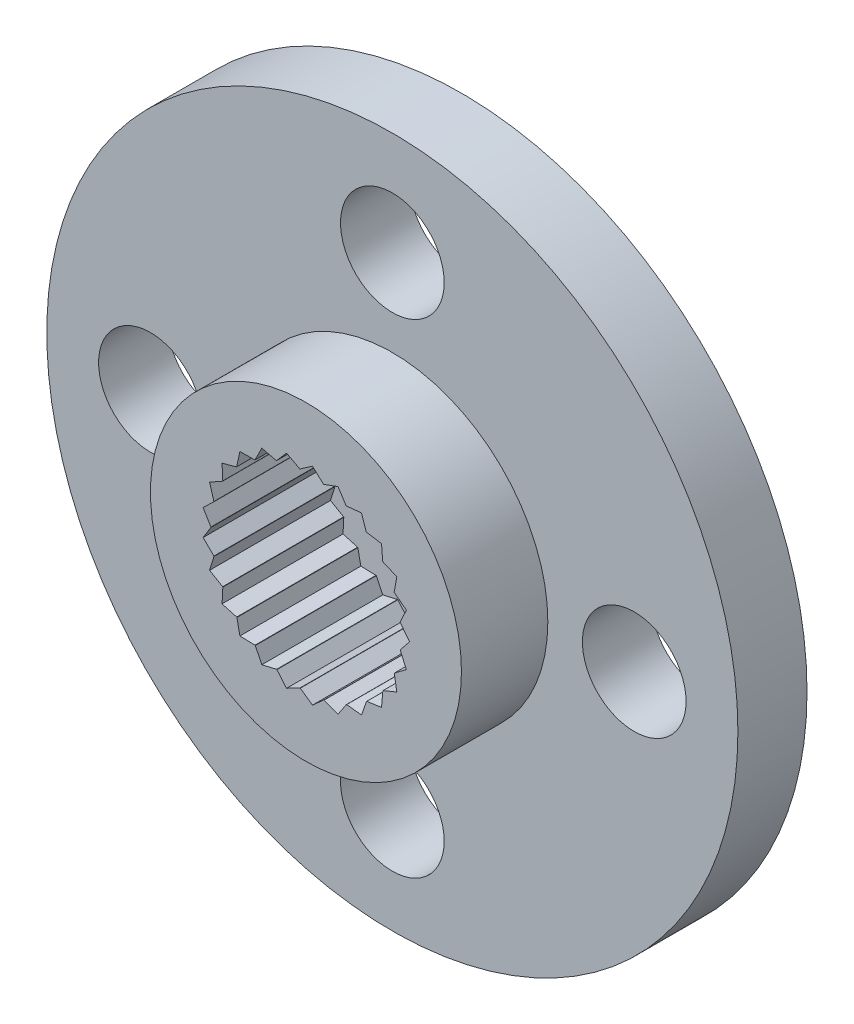
SolidWorks part; units mm, degrees
ref_plane "Front Plane" through (0, 0, 0) normal (0, 0, 1) x (1, 0, 0)
ref_plane "Top Plane" through (0, 0, 0) normal (0, 1, 0) x (1, 0, 0)
ref_plane "Right Plane" through (0, 0, 0) normal (1, 0, 0) x (0, 0, -1)
sketch "Sketch1" plane through (0, 0, 0) normal (0, 0, 1) x (1, 0, 0)
  circle A0 centre (0, 0) radius 10
  circle A1 centre (0, 0) radius 7 construction
  circle A2 centre (0, 7) radius 1.5
  circle A3 centre (7, 0) radius 1.5
  circle A4 centre (0, -7) radius 1.5
  circle A5 centre (-7, 0) radius 1.5
  circle A6 centre (0, 0) radius 4.5
  dimension "D1" = 20
  dimension "D2" = 3
  dimension "D3" = 4
extrude "Boss-Extrude1" add sketch "Sketch1" along normal blind 2
extrude "Boss-Extrude2" add sketch "Sketch1<2>" along normal blind 4.5 contours A6 region at (0, 0, 0)
sketch "Sketch1<2>" plane through (0, 0, 0) normal (0, 0, 1) x (1, 0, 0) same geometry as "Sketch1"
sketch "Sketch2" plane through (0, 0, 0) normal (0, 0, -1) x (-1, 0, 0)
  circle A0 centre (0, 0) radius 1.5
extrude "Cut-Extrude1" cut sketch "Sketch2" against normal blind 4.5
sketch "Sketch3" plane through (0, 0, 4.5) normal (0, 0, 1) x (1, 0, 0)
  circle A0 centre (0, 0) radius 2.75
extrude "Cut-Extrude2" cut sketch "Sketch3" against normal blind 3.5
sketch "Sketch4" plane through (0, 0, 4.5) normal (0, 0, 1) x (1, 0, 0)
  line L0 (0, 0) -> (-3, 0)
  line L1 (0, 0) -> (-2.9763, 0.376)
  line L2 (0, 0) -> (-2.9083, 0.7359)
  line L3 (-2.75, 0) -> (-2.9763, 0.376)
  line L4 (-2.666, 0.6746) -> (-2.9763, 0.376)
  circle A0 centre (0, 0) radius 3
  circle A1 centre (0, 0) radius 2.75 construction
  circle A2 centre (0, 0) radius 2.75 construction
  circle A3 centre (0, 0) radius 2.75
  circle M6 centre (0, 0) radius 2.75
  dimension "D1" = 7.2
  dimension "D2" = 14.2
extrude "Cut-Extrude3" cut sketch "Sketch4" against normal blind 3.5 contours L4 L1 M6 | L3 L1 M6 region at (-2.8205, 0.2422, 4.5) region at (-2.7928, 0.4638, 4.5)
pattern_circular "CirPattern1" count 25 over 360 about axis through (0, 0, 4.5) along (0, 0, -1) of "Cut-Extrude3" reverse direction yes
